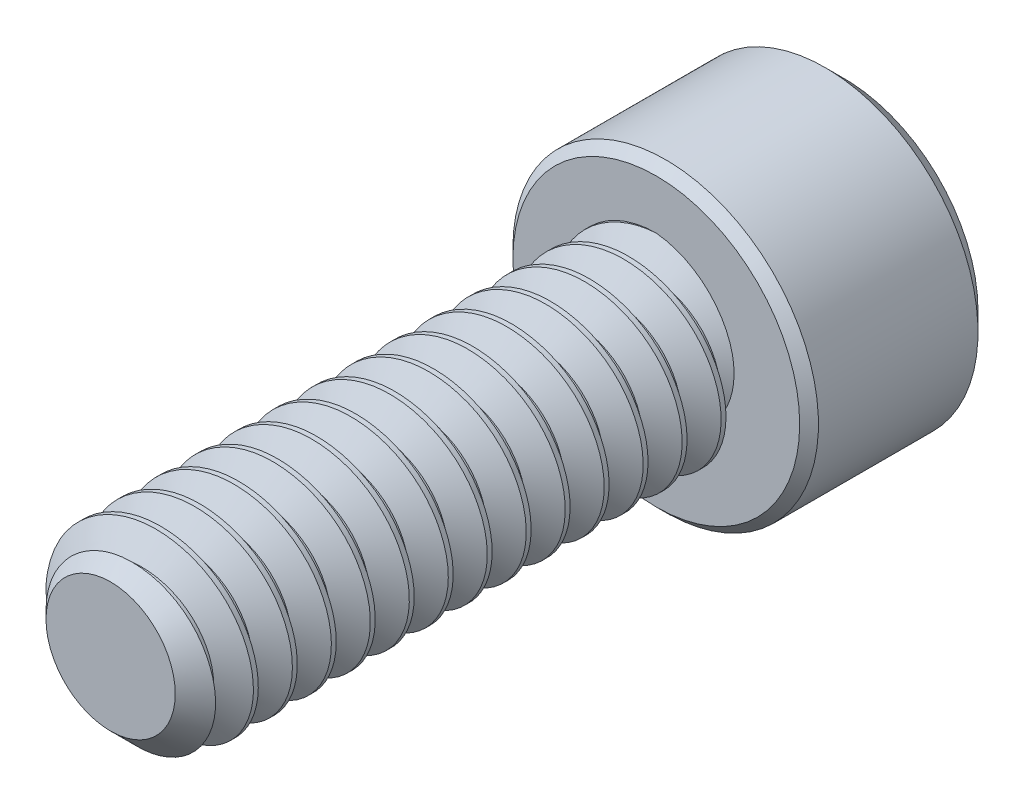
SolidWorks part; units mm, degrees
ref_plane "Front Plane" through (0, 0, 0) normal (0, 0, 1) x (1, 0, 0)
ref_plane "Top Plane" through (0, 0, 0) normal (0, 1, 0) x (1, 0, 0)
ref_plane "Right Plane" through (0, 0, 0) normal (1, 0, 0) x (0, 0, -1)
sketch "Sketch1" plane through (0, 0, 0) normal (0, 0, 1) x (1, 0, 0)
  line L0 (0, 1.0922) -> (0, -1.0922) construction
  circle A0 centre (0, 0) radius 1.0922
  dimension "OD" = 2.1844
extrude "Extrude1" add sketch "Sketch1" against normal blind 6.35
sketch "Sketch2" plane through (0, 0, 0) normal (0, 0, 1) x (1, 0, 0)
  circle A0 centre (0, 0) radius 1.0922 construction
  circle A1 centre (0, 0) radius 1.0922
curve "Helix/Spiral1" pitch 0.4536 height 6.8036 radius 1.0922 centre (0, 0, 0) axis (0, 0, -1) start towards (0, 1, 0) parameters "pitch"=0.4536
chamfer "Chamfer3" distance 0.3402 angle 45 1 edges at (1.0922, 0, 0)
sketch "Sketch3" plane through (0, 0, 0) normal (1, 0, 0) x (0, 0, -1)
  line L0 (-0.3969, 1.0922) -> (-0.2268, 0.7976)
  line L1 (-0.2268, 0.7976) -> (-0.1701, 0.7976)
  line L2 (-0.1701, 0.7976) -> (0, 1.0922)
  line L3 (-0.3969, 1.0922) -> (0, 1.0922)
  line L4 (-0.1984, 1.0922) -> (-0.1984, 0.7976) construction
  line L5 (-0.3118, 0.9449) -> (-0.085, 0.9449) construction
  line L6 (0, 1.0922) -> (0, -1.0922) construction
  dimension "D1" = 0.0567
  dimension "D2" = 0.2268
  dimension "D3" = 60
sweep "Cut-Sweep1" cut profiles "Sketch3" path "Helix/Spiral1"
sketch "Sketch6" plane through (0, 0, -6.35) normal (0, 0, -1) x (-1, 0, 0)
  circle A0 centre (0, 0) radius 1.778
  dimension "head dia" = 3.556
extrude "Extrude2" add sketch "Sketch6" along normal blind 2.1844
sketch "Sketch7" plane through (0, 0, -8.5344) normal (0, 0, -1) x (-1, 0, 0)
  line L1 (0, 1.1457) -> (-0.9922, 0.5728)
  line L2 (-0.9922, 0.5728) -> (-0.9922, -0.5728)
  line L3 (-0.9922, -0.5728) -> (0, -1.1457)
  line L4 (0, -1.1457) -> (0.9922, -0.5728)
  line L5 (0.9922, -0.5728) -> (0.9922, 0.5728)
  line L6 (0.9922, 0.5728) -> (0, 1.1457)
  circle A0 centre (0, 0) radius 0.9922 construction
  dimension "hex dia" = 1.9844
extrude "Cut-Extrude1" cut sketch "Sketch7" against normal blind 1.4883
sketch "Sketch8" plane through (0, 0, -8.5344) normal (0, 0, -1) x (-1, 0, 0)
  circle A0 centre (0, 0) radius 1.1457
extrude "Cut-Extrude2" cut sketch "Sketch8" against normal blind 0.2184 draft 45
chamfer "Chamfer1" distance 0.2184 angle 45 1 edges at (-1.778, 0, -8.5344)
chamfer "Chamfer2" distance 0.1092 angle 45 1 edges at (-1.778, 0, -6.35)
sketch "Sketch9" plane through (0, 0, 0) normal (1, 0, 0) x (0, 0, -1)
  line L0 (0, 1.0922) -> (0, -1.0922) construction
  line L1 (2.4946, 1.0922) -> (2.4946, -1.0922) construction
  line L2 (6.35, 1.778) -> (6.35, -1.778) construction
  line L3 (8.5344, 1.778) -> (8.5344, -1.778) construction
  line L4 (8.5344, 0) -> (0, 0) construction
  dimension "D1" = 2.4946
  dimension "D2" = 2.1844
  dimension "D3" = 3.556
  dimension "D4" = 6.35
equation "\"D3@Helix/Spiral1\" = \"screw length@Extrude1\"+\"pitch@Helix/Spiral1\""
equation "\"D1@Sketch3\" = \"pitch@Helix/Spiral1\"*.125"
equation "\"D2@Sketch3\" = \"pitch@Helix/Spiral1\"*.5"
equation "\"D1@Cut-Extrude1\" = \"hex dia@Sketch7\"*.75"
equation "\"D1@Chamfer1\" = \"head depth@Extrude2\"/10"
equation "\"D1@Sketch9\" = \"pitch@Helix/Spiral1\"*5.5"
equation "\"D1@Chamfer2\" = \"D1@Chamfer1\"/2"
equation "\"D1@Cut-Extrude2\" = \"D1@Chamfer2\"*2"
equation "\"D1@Chamfer3\" = \"pitch@Helix/Spiral1\"*.750"
equation "\"D2@Sketch9\" = \"head depth@Extrude2\""
equation "\"D3@Sketch9\" = \"head dia@Sketch6\""
equation "\"D4@Sketch9\" = \"screw length@Extrude1\""
